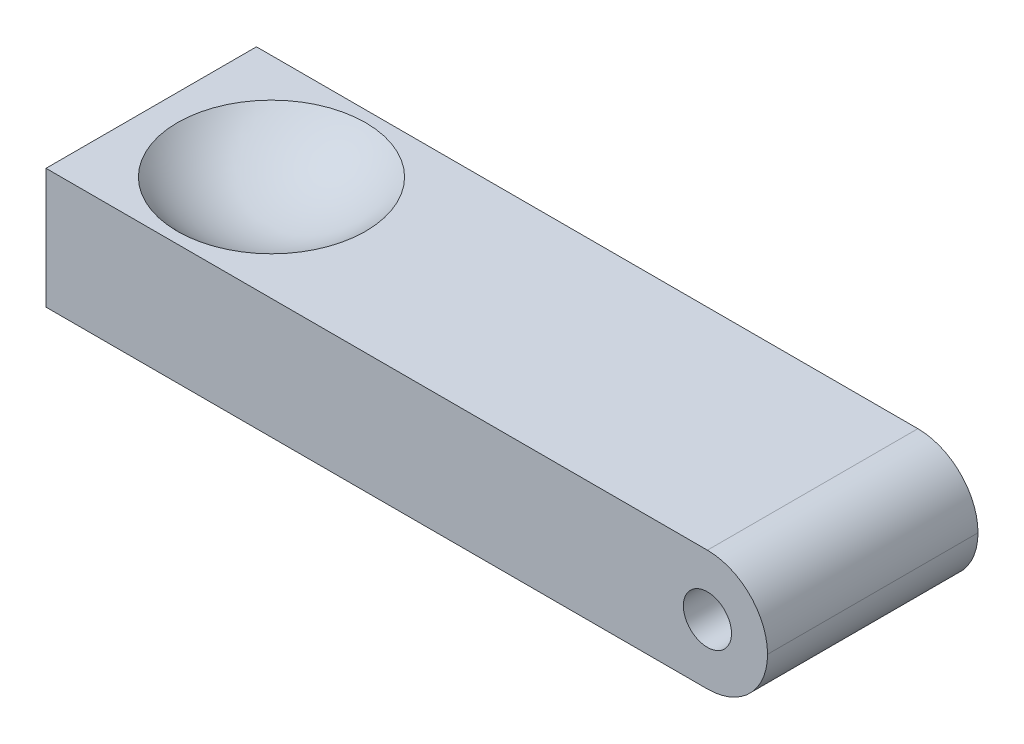
SolidWorks part; units mm, degrees
ref_plane "Front" through (0, 0, 0) normal (0, 0, 1) x (1, 0, 0)
ref_plane "Top" through (0, 0, 0) normal (0, 1, 0) x (1, 0, 0)
ref_plane "Right" through (0, 0, 0) normal (1, 0, 0) x (0, 0, -1)
sketch "Sketch1" plane through (0, 0, 0) normal (0, 1, 0) x (1, 0, 0)
  line L1 (-60, 17.5) -> (60, 17.5)
  line L2 (-60, 17.5) -> (-60, -17.5)
  line L3 (-60, -17.5) -> (60, -17.5)
  line L4 (60, 17.5) -> (60, -17.5)
  line L5 (-60, 17.5) -> (60, -17.5) construction
  line L6 (-60, -17.5) -> (60, 17.5) construction
  point P0 (0, 0)
  dimension "D1" = 35
  dimension "D2" = 120
extrude "Boss-Extrude1" add sketch "Sketch1" along normal mid plane 20
fillet "Fillet1" radius 10 2 edges at (60, 10, 0) (60, -10, 0)
sketch "Sketch2" plane through (0, 0, 0) normal (0, 0, 1) x (1, 0, 0)
  line L0 (-60, 10) -> (-60, -10) construction
  line L1 (-60, 10) -> (50, 10) construction
  line L2 (-61, 24) -> (-19, 24)
  arc A0 (-19, 24) -> (-61, 24) centre (-40, 24) ccw
  dimension "D1" = 42
  dimension "D2" = 20
  dimension "D3" = 14
revolve "Cut-Revolve1" cut sketch "Sketch2" angle 360 about L2
hole_wizard "Ø8.0mm Dowel Hole1" positions "Sketch3" profile "Sketch4" hole size "Ø8.0" standard "ANSI Metric" end condition through all
sketch "Sketch3" plane through (0, 0, 17.5) normal (0, 0, 1) x (1, 0, 0)
  point P0 (50, 0)
sketch "Sketch4" plane through (50, 0, 17.5) normal (1, 0, 0) x (0, -1, 0)
  line L0 (0, 0) -> (0, 35)
  line L1 (0, 35) -> (4, 35)
  line L2 (4, 35) -> (4, 0)
  line L5 (4, 0) -> (0, 0)
  line L11 (0, -6.35) -> (0, 107.95) construction
  dimension "Thru Hole Dia." = 8
  dimension "Thru Hole Depth" = 35
